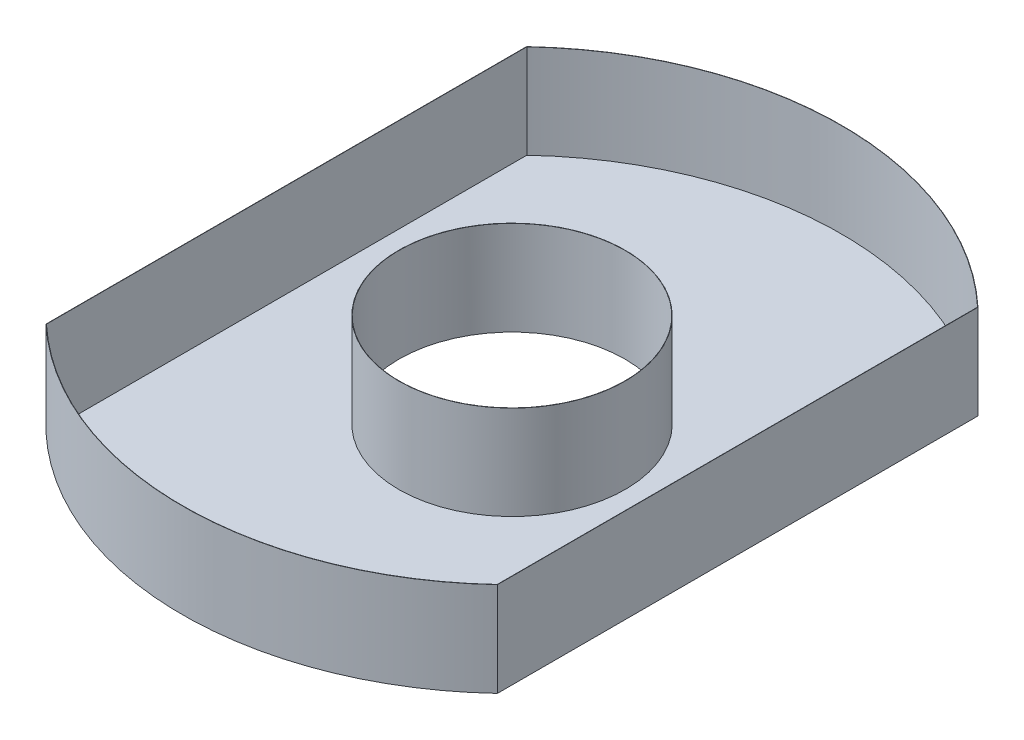
SolidWorks part; units mm, degrees
material "1345 Alloy"
ref_plane "Front Plane" through (0, 0, 0) normal (0, 0, 1) x (1, 0, 0)
ref_plane "Top Plane" through (0, 0, 0) normal (0, 1, 0) x (1, 0, 0)
ref_plane "Right Plane" through (0, 0, 0) normal (1, 0, 0) x (0, 0, -1)
sketch "Sketch1" plane through (0, 0, 0) normal (0, 1, 0) x (1, 0, 0)
  circle A0 centre (0, 0) radius 1750
extrude "Boss-Extrude1" add sketch "Sketch1" along normal blind 500
sketch "Sketch3" plane through (0, 0, 0) normal (0, -1, 0) x (1, 0, 0)
  circle A0 centre (0, 0) radius 600
extrude "Cut-Extrude3" cut sketch "Sketch3" against normal through all both and the other way through all
ref_plane "Plane1" through (0, 0, 2000) normal (0, 0, 1) x (1, 0, 0)
sketch "Sketch7" plane through (0, 0, 2000) normal (0, 0, 1) x (1, 0, 0)
  circle A0 centre (0, 133.8976) radius 8.382
extrude "Cut-Extrude6" [suppressed] cut sketch "Sketch7" against normal blind 900
pattern_circular "CirPattern1" [suppressed] count 4 over 360 reverse direction yes of bodies 107
ref_plane "Plane2" through (-1237.4369, 0, 1237.4369) normal (-0.7071, 0, 0.7071) x (0, -1, 0)
sketch "Sketch9" plane through (0, 0, 0) normal (0, -1, 0) x (-1, 0, 0)
  line L1 (1198.0599, -2169.9586) -> (-1198.0599, -2169.9586)
  line L2 (1198.0599, -2169.9586) -> (1198.0599, 2169.9586)
  line L3 (1198.0599, 2169.9586) -> (-1198.0599, 2169.9586)
  line L4 (-1198.0599, -2169.9586) -> (-1198.0599, 2169.9586)
  line L5 (1198.0599, -2169.9586) -> (-1198.0599, 2169.9586) construction
  line L6 (1198.0599, 2169.9586) -> (-1198.0599, -2169.9586) construction
  line L7 (2079.6689, -2697.8613) -> (-2079.6689, -2697.8613)
  line L8 (2079.6689, -2697.8613) -> (2079.6689, 2697.8613)
  line L9 (2079.6689, 2697.8613) -> (-2079.6689, 2697.8613)
  line L10 (-2079.6689, -2697.8613) -> (-2079.6689, 2697.8613)
  line L11 (2079.6689, -2697.8613) -> (-2079.6689, 2697.8613) construction
  line L12 (2079.6689, 2697.8613) -> (-2079.6689, -2697.8613) construction
  point P0 (0, 0)
  point P6 (0, 0)
extrude "Cut-Extrude9" cut sketch "Sketch9" against normal through all both and the other way through all
shell "Shell1" thickness 1.5 removed face at (0, 500, -600)
